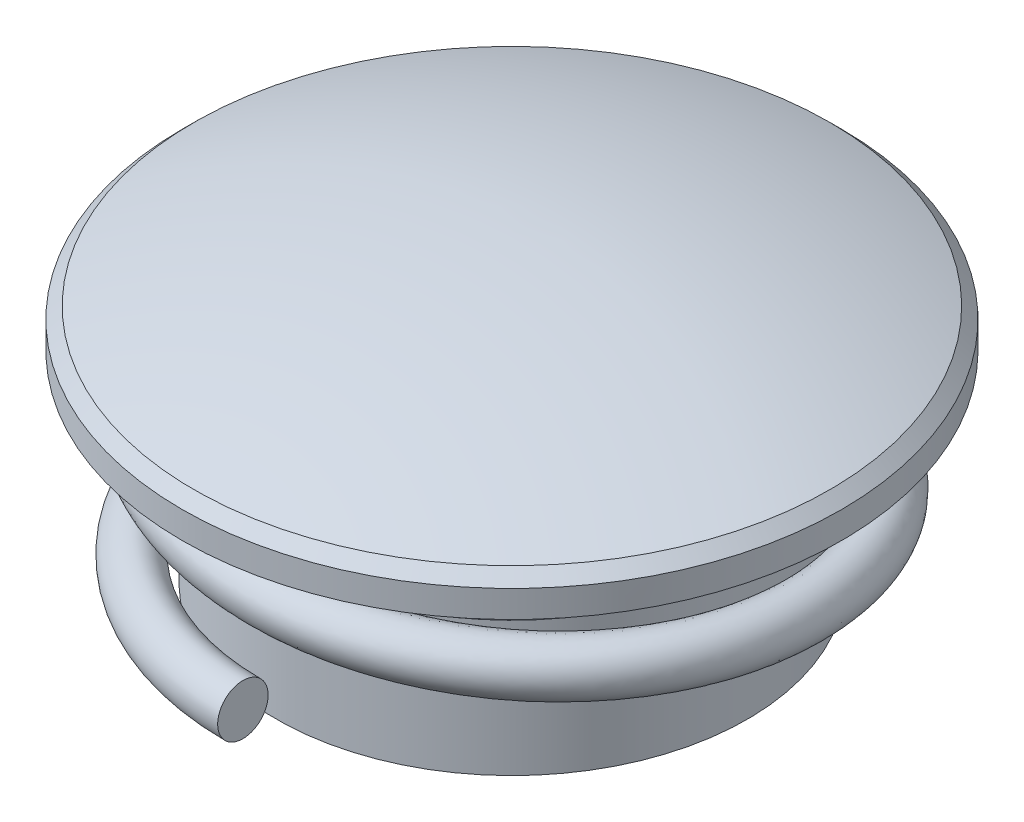
SolidWorks part; units mm, degrees
ref_plane "Front Plane" through (0, 0, 0) normal (0, 0, 1) x (1, 0, 0)
ref_plane "Top Plane" through (0, 0, 0) normal (0, 1, 0) x (1, 0, 0)
ref_plane "Right Plane" through (0, 0, 0) normal (1, 0, 0) x (0, 0, -1)
sketch "Sketch1" plane through (0, 0, 0) normal (0, 1, 0) x (1, 0, 0)
  circle A0 centre (0, 0) radius 4.9
  dimension "D1" = 9.8
extrude "Boss-Extrude1" add sketch "Sketch1" along normal blind 0.5
dome "Dome1" faces to dome 1 distance 1 reverse direction no elliptical dome no face at (0, 0.5, 4.9) parameters "D1"=1
sketch "Sketch2" plane through (0, 0, 0) normal (0, -1, 0) x (1, 0, 0)
  circle A0 centre (0, 0) radius 1
  dimension "D1" = 2
extrude "Boss-Extrude2" add sketch "Sketch2" along normal blind 4
ref_plane "Plane1" through (0, -3, 0) normal (0, -1, 0) x (-1, 0, 0)
sketch "Sketch3" plane through (0, -3, 0) normal (0, -1, 0) x (-1, 0, 0)
  circle A0 centre (0, 0) radius 3.5
  dimension "D1" = 7
extrude "Boss-Extrude3" add sketch "Sketch3" against normal blind 2
ref_plane "Plane2" through (0, -0.375, 0) normal (0, -1, 0) x (-1, 0, 0)
sketch "Sketch5" plane through (0, -0.375, 0) normal (0, -1, 0) x (-1, 0, 0)
  circle A0 centre (0, 0) radius 4
  dimension "D1" = 8
curve "Helix/Spiral1" pitch 2.25 height 2.25 radius 4 left hand yes centre (0, -0.375, 0) axis (0, -1, 0) start towards (0, 0, -1)
sketch "Sketch6" plane through (0, -0.375, 0) normal (0, -1, 0) x (-1, 0, 0)
  line L0 (0, 0) -> (4, 0) construction
  point P4 (4, 0)
  dimension "D1" = 4
sketch "Sketch7" plane through (0, 0, 0) normal (0, 0, 1) x (1, 0, 0)
  circle A0 centre (-4, -0.375) radius 0.375
  dimension "D1" = 0.75
sweep "Sweep1" add profiles "Sketch7" path "Helix/Spiral1"
sketch "Sketch8" plane through (0, -0.375, 0) normal (0, -1, 0) x (-1, 0, 0)
  line L0 (0, 0) -> (0, 4) construction
  line L1 (0, 0) -> (4, 0) construction
  arc A0 (4, 0) -> (0, 4) centre (0, 0) ccw
  dimension "D1" = 8
sketch "Sketch9" plane through (0, 0, 0) normal (0, 0, -1) x (-1, 0, 0)
  circle A0 centre (4, -0.375) radius 0.375
sweep "Sweep2" add profiles "Sketch9" path "Sketch8"
ref_plane "Plane3" through (0, -2.625, 0) normal (0, -1, 0) x (-1, 0, 0)
sketch "Sketch10" plane through (0, -2.625, 0) normal (0, -1, 0) x (-1, 0, 0)
  line L0 (0, 0) -> (0, -4) construction
  line L1 (0, 0) -> (4, 0) construction
  arc A0 (0, -4) -> (4, 0) centre (0, 0) ccw
  dimension "D1" = 8
sketch "Sketch11" plane through (0, 0, 0) normal (0, 0, 1) x (1, 0, 0)
  line L0 (-4, -2.625) -> (0, -2.625) construction
  circle A0 centre (-4, -2.625) radius 0.375
  spline S0 degree 3 poles (-4, -0.375) (-4, -0.4216) (-3.7917, -0.5158) (-2.9021, -0.6562) (-1.5706, -0.7969) (0, -0.9375) (1.5706, -1.0781) (2.9021, -1.2187) (3.7917, -1.3594) (4.1041, -1.5) (3.7917, -1.6406) (2.9021, -1.7813) (1.5706, -1.9219) (0, -2.0625) (-1.5706, -2.2031) (-2.9021, -2.3438) (-3.7917, -2.4842) (-4, -2.5784) (-4, -2.625) knots 0 0 0 0 0.0625 0.125 0.1875 0.25 0.3125 0.375 0.4375 0.5 0.5625 0.625 0.6875 0.75 0.8125 0.875 0.9375 1 1 1 1 construction
sweep "Sweep3" add profiles "Sketch11" path "Sketch10"
sketch "Sketch13" plane through (0, -4, 0) normal (0, -1, 0) x (1, 0, 0)
  circle A0 centre (0, 0) radius 2
  dimension "D1" = 4
ref_plane "Plane4" through (0, -3.5, 0) normal (0, -1, 0) x (-1, 0, 0)
sketch "Sketch14" plane through (0, -3.5, 0) normal (0, -1, 0) x (-1, 0, 0)
  circle A0 centre (0, 0) radius 2
extrude "Boss-Extrude4" add sketch "Sketch14" along normal blind 0.2
sketch "Sketch15" plane through (0, -3.7, 0) normal (0, -1, 0) x (1, 0, 0)
  line L0 (0, 1) -> (0, 2)
  line L1 (0.6428, 0.766) -> (1.2856, 1.5321)
  circle A0 centre (0, 0) radius 2 construction
  arc A1 (0, 2) -> (1.2856, 1.5321) centre (0, 0) cw
  arc A2 (0, 1) -> (0.6428, 0.766) centre (0, 0) cw
  dimension "D1" = 40
extrude "Cut-Extrude1" cut sketch "Sketch15" against normal up to next (0.2 mm away)
fillet "Fillet1" radius 0.3 2 edges at (1.2856, -3.6, 1.5321) (0, -3.6, 2)
chamfer "Chamfer1" distance 0.1 angle 45 1 edges at (0, 0.5, 4.9) first distance on face at (0, 0.5, 4.9)
